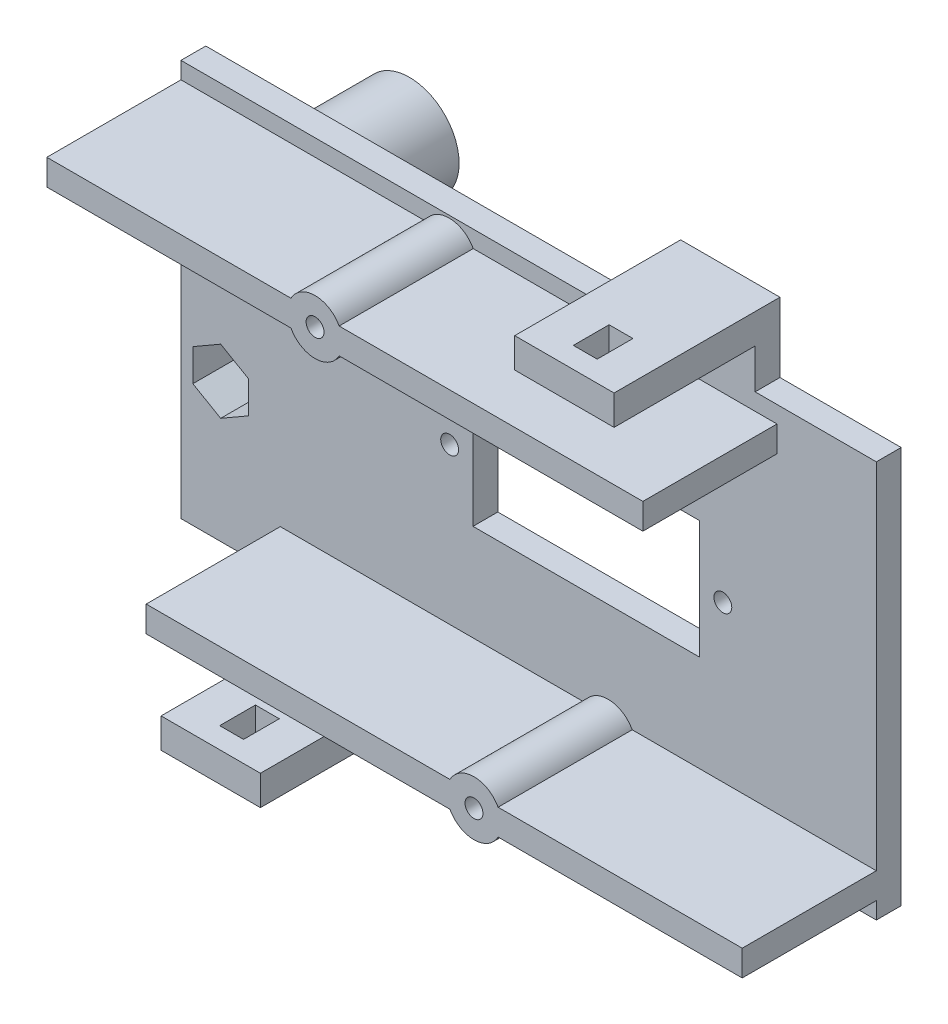
SolidWorks part; units mm, degrees
ref_plane "Front Plane" through (0, 0, 0) normal (0, 0, 1) x (1, 0, 0)
ref_plane "Top Plane" through (0, 0, 0) normal (0, 1, 0) x (1, 0, 0)
ref_plane "Right Plane" through (0, 0, 0) normal (1, 0, 0) x (0, 0, -1)
sketch "Sketch1" plane through (0, 0, 0) normal (0, 0, 1) x (1, 0, 0)
  line L0 (-35, -19.975) -> (35, -19.975)
  line L1 (35, -19.975) -> (35, 19.975)
  line L2 (35, 19.975) -> (-35, 19.975)
  line L3 (-35, 19.975) -> (-35, -19.975)
extrude "Boss-Extrude1" add sketch "Sketch1" along normal blind 2.5 from offset 2.5 offset against normal yes
sketch "Sketch2" plane through (0, 0, 0) normal (0, 0, 1) x (1, 0, 0)
  line L0 (-35, 15.675) -> (25, 15.675)
  line L1 (25, 15.675) -> (25, 18.275)
  line L2 (25, 18.275) -> (-35, 18.275)
  line L3 (-35, 18.275) -> (-35, 15.675)
extrude "Boss-Extrude2" add sketch "Sketch2" along normal blind 13.5
sketch "Sketch3" plane through (0, 0, 0) normal (0, 0, 1) x (1, 0, 0)
  line L0 (-25, -18.275) -> (35, -18.275)
  line L1 (35, -18.275) -> (35, -15.675)
  line L2 (35, -15.675) -> (-25, -15.675)
  line L3 (-25, -15.675) -> (-25, -18.275)
extrude "Boss-Extrude3" add sketch "Sketch3" along normal blind 13.5
sketch "Sketch4" plane through (0, 0, 0) normal (0, 0, 1) x (1, 0, 0)
  circle A0 centre (-8, 16.975) radius 2.75
  circle A1 centre (8, -16.975) radius 2.75
extrude "Boss-Extrude4" add sketch "Sketch4" along normal blind 13.5
sketch "Sketch5" plane through (0, 0, 0) normal (0, 0, 1) x (1, 0, 0)
  circle A0 centre (-31, 6) radius 5
  circle A1 centre (-31, -6) radius 5
extrude "Boss-Extrude5" add sketch "Sketch5" along normal blind 16.5 from offset 19 offset against normal yes
sketch "Sketch6" plane through (0, 0, 0) normal (0, 0, 1) x (1, 0, 0)
  line L0 (-5.6, -5.95) -> (17.2, -5.95)
  line L1 (17.2, -5.95) -> (17.2, 5.95)
  line L2 (17.2, 5.95) -> (-5.6, 5.95)
  line L3 (-5.6, 5.95) -> (-5.6, -5.95)
extrude "Cut-Extrude1" cut sketch "Sketch6" against normal through all and the other way through all
sketch "Sketch7" plane through (0, 0, 0) normal (0, 0, 1) x (1, 0, 0)
  circle A0 centre (-7.95, 0) radius 0.9
  circle A1 centre (19.55, 0) radius 0.9
extrude "Cut-Extrude2" cut sketch "Sketch7" against normal through all and the other way through all
sketch "Sketch8" plane through (0, 0, 0) normal (0, 0, 1) x (1, 0, 0)
  circle A0 centre (-8, 16.975) radius 0.9
  circle A1 centre (8, -16.975) radius 0.9
extrude "Cut-Extrude3" cut sketch "Sketch8" against normal through all and the other way through all
sketch "Sketch9" plane through (0, 0, 0) normal (0, 0, 1) x (1, 0, 0)
  line L0 (12.8, 19.975) -> (22.8, 19.975)
  line L1 (22.8, 19.975) -> (22.8, 26.975)
  line L2 (22.8, 26.975) -> (12.8, 26.975)
  line L3 (12.8, 26.975) -> (12.8, 19.975)
extrude "Boss-Extrude6" add sketch "Sketch9" along normal blind 2.5 from offset 2.5 offset against normal yes
sketch "Sketch10" plane through (0, 0, 0) normal (0, 0, 1) x (1, 0, 0)
  line L0 (12.8, 23.975) -> (22.8, 23.975)
  line L1 (22.8, 23.975) -> (22.8, 26.975)
  line L2 (22.8, 26.975) -> (12.8, 26.975)
  line L3 (12.8, 26.975) -> (12.8, 23.975)
extrude "Boss-Extrude7" add sketch "Sketch10" along normal blind 14.2
sketch "Sketch11" plane through (0, 0, 0) normal (0, 0, 1) x (1, 0, 0)
  line L0 (-12.8, -19.975) -> (-22.8, -19.975)
  line L1 (-22.8, -19.975) -> (-22.8, -26.975)
  line L2 (-22.8, -26.975) -> (-12.8, -26.975)
  line L3 (-12.8, -26.975) -> (-12.8, -19.975)
extrude "Boss-Extrude8" add sketch "Sketch11" along normal blind 2.5 from offset 2.5 offset against normal yes
sketch "Sketch12" plane through (0, 0, 0) normal (0, 0, 1) x (1, 0, 0)
  line L0 (-12.8, -23.975) -> (-22.8, -23.975)
  line L1 (-22.8, -23.975) -> (-22.8, -26.975)
  line L2 (-22.8, -26.975) -> (-12.8, -26.975)
  line L3 (-12.8, -26.975) -> (-12.8, -23.975)
extrude "Boss-Extrude9" add sketch "Sketch12" along normal blind 14.2
sketch "Sketch13" plane through (0, 0, 0) normal (0, 0, 1) x (1, 0, 0)
  circle A0 centre (-31, 6) radius 1.725
  circle A1 centre (-31, -6) radius 1.725
extrude "Cut-Extrude4" cut sketch "Sketch13" against normal through all and the other way through all
sketch "Sketch14" plane through (0, 0, 0) normal (0, 0, 1) x (1, 0, 0)
  line L0 (-28.2, 7.6166) -> (-31, 9.2332)
  line L1 (-31, 9.2332) -> (-33.8, 7.6166)
  line L2 (-33.8, 7.6166) -> (-33.8, 4.3834)
  line L3 (-33.8, 4.3834) -> (-31, 2.7668)
  line L4 (-31, 2.7668) -> (-28.2, 4.3834)
  line L5 (-28.2, 4.3834) -> (-28.2, 7.6166)
  line L6 (-28.2, -4.3834) -> (-31, -2.7668)
  line L7 (-31, -2.7668) -> (-33.8, -4.3834)
  line L8 (-33.8, -4.3834) -> (-33.8, -7.6166)
  line L9 (-33.8, -7.6166) -> (-31, -9.2332)
  line L10 (-31, -9.2332) -> (-28.2, -7.6166)
  line L11 (-28.2, -7.6166) -> (-28.2, -4.3834)
extrude "Cut-Extrude5" cut sketch "Sketch14" along normal blind 4.2 from offset 4.2 offset against normal yes
sketch "Sketch15" plane through (0, 0, 0) normal (0, 1, 0) x (1, 0, 0)
  line L0 (16.6, -8.5) -> (19, -8.5)
  line L1 (19, -8.5) -> (19, -12.1)
  line L2 (19, -12.1) -> (16.6, -12.1)
  line L3 (16.6, -12.1) -> (16.6, -8.5)
extrude "Cut-Extrude6" cut sketch "Sketch15" against normal mid plane 4 from offset 25.475
sketch "Sketch16" plane through (0, 0, 0) normal (0, 1, 0) x (1, 0, 0)
  line L0 (-19, -8.5) -> (-16.6, -8.5)
  line L1 (-16.6, -8.5) -> (-16.6, -12.1)
  line L2 (-16.6, -12.1) -> (-19, -12.1)
  line L3 (-19, -12.1) -> (-19, -8.5)
extrude "Cut-Extrude7" cut sketch "Sketch16" against normal mid plane 4 from offset 25.475 offset against normal yes
